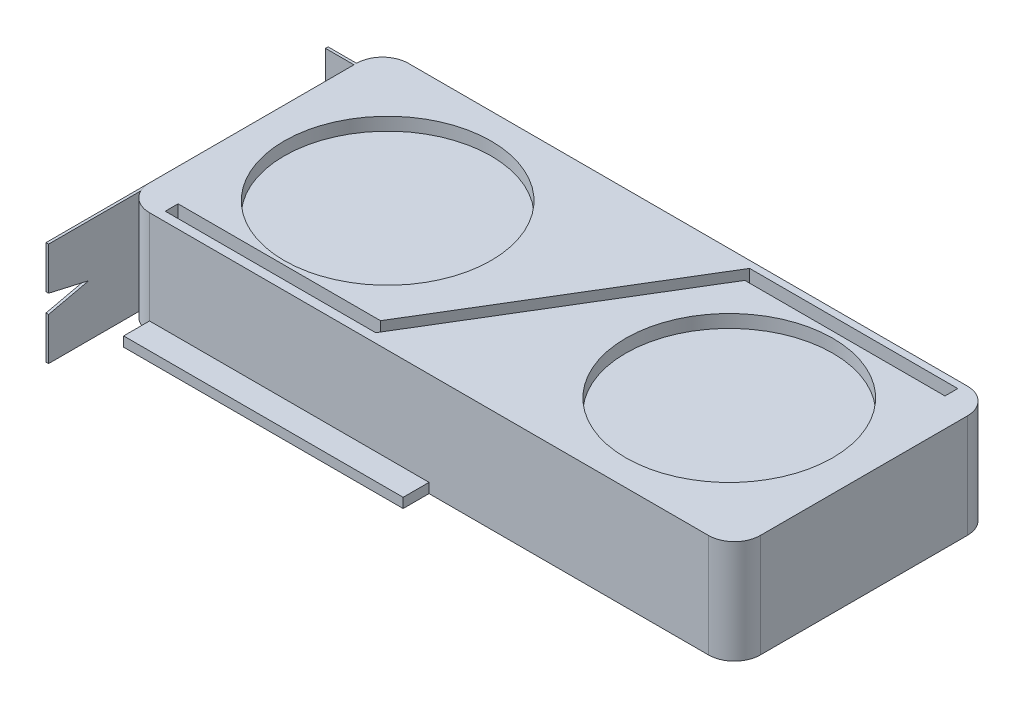
SolidWorks part; units mm, degrees
ref_plane "Front Plane" through (0, 0, 0) normal (0, 0, 1) x (1, 0, 0)
ref_plane "Top Plane" through (0, 0, 0) normal (0, 1, 0) x (1, 0, 0)
ref_plane "Right Plane" through (0, 0, 0) normal (1, 0, 0) x (0, 0, -1)
sketch "Sketch1" plane through (0, 0, 0) normal (0, 1, 0) x (1, 0, 0)
  line L1 (-118, 50) -> (118, 50)
  line L2 (-118, 50) -> (-118, -50)
  line L3 (-118, -50) -> (118, -50)
  line L4 (118, 50) -> (118, -50)
  line L5 (-118, 50) -> (118, -50) construction
  line L6 (-118, -50) -> (118, 50) construction
  point P0 (0, 0)
  dimension "D1" = 236
  dimension "D2" = 100
extrude "Boss-Extrude1" add sketch "Sketch1" along normal blind 40
sketch "Sketch2" plane through (0, 40, 0) normal (0, 1, 0) x (1, 0, 0)
  line L4 (0, -2) -> (0, 2)
  line L8 (-66, 0) -> (0, 0) construction
  line L9 (0, 0) -> (66, 0) construction
  circle A0 centre (-66, 0) radius 40
  circle A1 centre (66, 0) radius 40
  dimension "D2" = 80
  dimension "D1" = 66
  dimension "D3" = 4
extrude "Cut-Extrude1" cut sketch "Sketch2" against normal blind 5 contours A0 | A1 region at (-66, 40, 0) region at (66, 40, 0)
fillet "Fillet1" radius 10 4 edges at (118, 20, 50) (118, 20, -50) (-118, 20, 50) (-118, 20, -50)
sketch "Sketch3" plane through (0, 40, 0) normal (0, 1, 0) x (1, 0, 0)
  line L0 (-105.4631, -41.5021) -> (-105.4631, -46.455)
  line L1 (-105.4631, -46.455) -> (-24.1389, -46.455)
  line L2 (-24.1389, -46.455) -> (29.6601, 42.356)
  line L3 (29.6601, 42.356) -> (107.0002, 42.356)
  line L4 (107.0002, 42.356) -> (107.0002, 47.309)
  line L5 (107.0002, 47.309) -> (26.5579, 47.309)
  line L6 (26.5579, 47.309) -> (-27.2411, -41.5021)
  line L7 (-27.2411, -41.5021) -> (-105.4631, -41.5021)
extrude "Cut-Extrude2" cut sketch "Sketch3" against normal blind 10
sketch "Sketch4" plane through (0, 0, 50) normal (0, 0, 1) x (1, 0, 0)
  line L1 (-108, 0) -> (0, 0)
  line L2 (-108, 0) -> (-108, 3.7749)
  line L3 (-108, 3.7749) -> (0, 3.7749)
  line L4 (0, 0) -> (0, 3.7749)
extrude "Boss-Extrude2" add sketch "Sketch4" along normal blind 10
sketch "Sketch5" plane through (-118, 0, 0) normal (-1, 0, 0) x (0, 0, 1)
  line L0 (40, 40) -> (80, 40)
  line L1 (80, 40) -> (80, 23.5438)
  line L2 (80, 23.5438) -> (64.4647, 20)
  line L3 (64.4647, 20) -> (69.3151, 20) construction
  line L4 (64.4647, 20) -> (64.4647, 40) construction
  line L5 (64.4647, 20) -> (64.4647, 0) construction
  line L6 (40, 0) -> (80, 0)
  line L7 (80, 0) -> (80, 16.4562)
  line L8 (80, 16.4562) -> (64.4647, 20)
  line L9 (40, 40) -> (40, 0)
  line L10 (50, 40) -> (50, 3.7749) construction
  line L11 (40, 0) -> (50, 0) construction
  point P13 (64.4647, 20.9488)
  dimension "D1" = 30
extrude "Boss-Extrude3" add sketch "Sketch5" against normal blind 1 separate body
sketch "Sketch6" plane through (-118, 0, 0) normal (-1, 0, 0) x (0, 0, 1)
  line L0 (-40, 0) -> (40, 0) construction
  line L1 (-40, 40) -> (-39, 40)
  line L2 (-40, 40) -> (-40, 0)
  line L3 (-40, 0) -> (-39, 0)
  line L4 (-39, 40) -> (-39, 0)
  dimension "D1" = 1
extrude "Boss-Extrude4" add sketch "Sketch6" along normal blind 11
